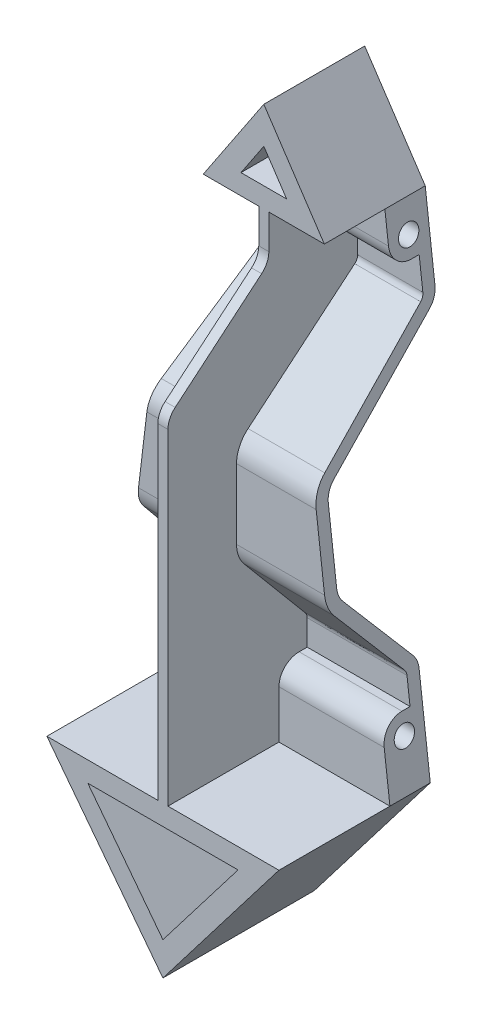
SolidWorks part; units mm, degrees
material "1060 Alloy"
ref_plane "Front Plane" through (0, 0, 0) normal (1, 0, 0) x (0, 1, 0)
ref_plane "Top Plane" through (0, 0, 0) normal (0, 0, 1) x (0, 1, 0)
ref_plane "Right Plane" through (0, 0, 0) normal (0, 1, 0) x (-1, 0, 0)
sketch "Sketch3" plane through (0, 0, 0) normal (1, 0, 0) x (0, 1, 0)
  line L0 (206.8578, 33.9279) -> (242.818, -8.9279)
  line L1 (-37.5, 37.5) -> (37.5, 37.5)
  line L2 (-37.5, 37.5) -> (-37.5, -37.5)
  line L3 (-37.5, -37.5) -> (37.5, -37.5)
  line L4 (37.5, 37.5) -> (37.5, -37.5)
  line L5 (-37.5, 37.5) -> (37.5, -37.5) construction
  line L6 (-37.5, -37.5) -> (37.5, 37.5) construction
  line L7 (37.5, 37.5) -> (199.1973, 37.5)
  line L8 (250.4785, -12.5) -> (267.5, -12.5)
  line L9 (267.5, -20.8097) -> (267.5, -62.5)
  line L10 (267.5, -62.5) -> (227.1631, -62.5)
  line L11 (219.5026, -58.9279) -> (175.1514, -6.0721)
  line L12 (167.4909, -2.5) -> (132.8511, -2.5)
  line L13 (126.4232, -4.8396) -> (90.2882, -35.1604)
  line L14 (83.8603, -37.5) -> (37.5, -37.5)
  line L15 (267.5, -12.5) -> (312.5, -12.5)
  line L16 (267.5, -12.5) -> (267.5, -62.5)
  line L17 (267.5, -62.5) -> (312.5, -62.5)
  line L18 (312.5, -12.5) -> (312.5, -62.5)
  arc A0 (206.8578, 33.9279) -> (199.1973, 37.5) centre (199.1973, 27.5) ccw
  arc A1 (242.818, -8.9279) -> (250.4785, -12.5) centre (250.4785, -2.5) ccw
  arc A2 (227.1631, -62.5) -> (219.5026, -58.9279) centre (227.1631, -52.5) cw
  arc A3 (175.1514, -6.0721) -> (167.4909, -2.5) centre (167.4909, -12.5) ccw
  arc A4 (132.8511, -2.5) -> (126.4232, -4.8396) centre (132.8511, -12.5) ccw
  arc A5 (90.2882, -35.1604) -> (83.8603, -37.5) centre (83.8603, -27.5) cw
  point P0 (0, 0)
  point P22 (222.5, -62.5)
  point P29 (87.5, -37.5)
  dimension "D13" = 10
  dimension "D14" = 10
  dimension "D15" = 10
  dimension "D1" = 75
  dimension "D2" = 75
  dimension "D3" = 50
  dimension "D4" = 45
  dimension "D5" = 60
  dimension "D6" = 35
  dimension "D7" = 130
  dimension "D8" = 230
  dimension "D11" = 50
  dimension "D9" = 50
  dimension "D10" = 50
  dimension "D12" = 45
extrude "Boss-Extrude1" add sketch "Sketch3" along normal mid plane 115 contours L4 L1 L2 L3 | A5 L13 A4 L12 A3 L11 A2 L10 L9 L4 L14 | L18 L15 L16 L9 L17 region at (0, 222.9167, 10.8879) region at (0, 0, 0) region at (0, 290, -37.5)
sketch "Sketch4" plane through (0, 0, 37.5) normal (0, 0, 1) x (1, 0, 0)
  line L0 (0, 390.4065) -> (0, -108.3244) construction
  line L1 (0, -37.5) -> (-57.5, 37.5)
  line L3 (-57.5, 37.5) -> (57.5, 37.5)
  line L5 (57.5, 37.5) -> (0, -37.5)
  line L6 (-57.5, 37.5) -> (-30, 267.5)
  line L7 (0, 294.4722) -> (-11.3148, 277.5)
  line L8 (-30, 267.5) -> (30, 267.5)
  line L10 (57.5, 37.5) -> (30, 267.5)
  line L11 (-30, 267.5) -> (0, 312.5)
  line L12 (57.5, 312.5) -> (-57.5, 312.5) construction
  line L13 (0, 312.5) -> (30, 267.5)
  line L14 (-11.3148, 277.5) -> (11.3148, 277.5)
  line L15 (11.3148, 277.5) -> (0, 294.4722)
  line L16 (-37.2326, 27.5) -> (37.2326, 27.5)
  line L17 (37.2326, 27.5) -> (0, -21.0643)
  line L18 (0, -21.0643) -> (-37.2326, 27.5)
  line L20 (-57.5, 250.4785) -> (-57.5, 312.5) construction
  line L22 (57.5, 250.4785) -> (57.5, 312.5) construction
  line L24 (-57.5, 312.5) -> (57.5, 312.5)
  line L26 (-57.5, 250.4785) -> (-57.5, 312.5)
  line L27 (57.5, 312.5) -> (-57.5, 312.5)
  line L28 (57.5, 250.4785) -> (57.5, 312.5)
  line L38 (-57.5, -37.5) -> (57.5, -37.5)
  line L39 (57.5, 312.5) -> (57.5, -37.5)
  line L40 (-57.5, 312.5) -> (57.5, 312.5)
  line L41 (-57.5, 312.5) -> (-57.5, -37.5)
  line L42 (-57.5, -37.5) -> (57.5, -37.5)
  line L43 (57.5, 312.5) -> (57.5, -37.5)
  dimension "D1" = 75
  dimension "D2" = 230
  dimension "D3" = 30
  dimension "D4" = 10
  dimension "D5" = 10
  dimension "D6" = 10
  dimension "D7" = 10
extrude "Cut-Extrude1" cut sketch "Sketch4" against normal through all contours L5 | L1 | L0 L16 L18 | L16 L0 L17 | L10 | L6 | L28 L27 L13 L10 | L6 L11 L27 L26 | L0 L7 L14 | L15 L0 L14 region at (43.4472, 229.2016, 37.5) region at (-43.4472, 229.2016, 37.5) region at (3.7716, 283.1574, 37.5) region at (-3.7716, 283.1574, 37.5) region at (-38.3333, -12.5, 37.5) region at (38.3333, -12.5, 37.5) region at (-12.4109, 11.3119, 37.5) region at (12.4109, 11.3119, 37.5)
sketch "Sketch6" plane through (61.1101, 7.3066, 0) normal (0.9929, 0.1187, 0) x (-0.1187, 0.9929, 0)
  line L0 (30.4084, -31.5) -> (77.0989, -31.5)
  line L1 (79.7319, -30.5507) -> (116.1243, -0.2298)
  line L2 (126.4386, 3.5) -> (161.3252, 3.5)
  line L3 (173.623, -2.1993) -> (218.2901, -55.0551)
  line L4 (221.4224, -56.5) -> (262.0466, -56.5)
  line L10 (30.4084, 37.5) -> (30.4084, -37.5)
  line L11 (30.4084, -37.5) -> (77.0989, -37.5)
  line L12 (83.5726, -35.1604) -> (119.965, -4.8396)
  line L13 (126.4386, -2.5) -> (161.3252, -2.5)
  line L14 (169.0402, -6.0721) -> (213.7074, -58.9279)
  line L15 (221.4224, -62.5) -> (262.0466, -62.5)
  line L16 (262.0466, -62.5) -> (262.0466, -12.5)
  line L19 (30.4084, 37.5) -> (30.4084, -37.5)
  line L20 (30.4084, -37.5) -> (77.0989, -37.5)
  line L21 (83.5726, -35.1604) -> (119.965, -4.8396)
  line L22 (126.4386, -2.5) -> (161.3252, -2.5)
  line L23 (169.0402, -6.0721) -> (213.7074, -58.9279)
  line L24 (221.4224, -62.5) -> (262.0466, -62.5)
  line L25 (262.0466, -62.5) -> (262.0466, -12.5)
  line L33 (262.0466, -12.5) -> (244.9038, -12.5)
  line L34 (237.1888, -8.9279) -> (200.9724, 33.9279)
  line L35 (237.1888, -8.9279) -> (200.9724, 33.9279)
  line L36 (193.2574, 37.5) -> (30.4084, 37.5)
  line L37 (193.2574, 37.5) -> (30.4084, 37.5)
  line L38 (262.0466, -12.5) -> (244.9038, -12.5)
  ellipse E5 centre (77.0989, -27.5) end of major axis (87.1701, -27.5) minor radius 10 (77.0989, -37.5) -> (83.5726, -35.1604) ccw
  ellipse E6 centre (126.4386, -12.5) end of major axis (136.5099, -12.5) minor radius 10 (126.4386, -2.5) -> (119.965, -4.8396) ccw
  ellipse E7 centre (161.3252, -12.5) end of major axis (171.3965, -12.5) minor radius 10 (169.0402, -6.0721) -> (161.3252, -2.5) ccw
  ellipse E8 centre (221.4224, -52.5) end of major axis (231.4936, -52.5) minor radius 10 (213.7074, -58.9279) -> (221.4224, -62.5) ccw
  ellipse E10 centre (77.0989, -27.5) end of major axis (87.1701, -27.5) minor radius 10 (77.0989, -37.5) -> (83.5726, -35.1604) ccw
  ellipse E11 centre (126.4386, -12.5) end of major axis (136.5099, -12.5) minor radius 10 (126.4386, -2.5) -> (119.965, -4.8396) ccw
  ellipse E12 centre (161.3252, -12.5) end of major axis (171.3965, -12.5) minor radius 10 (169.0402, -6.0721) -> (161.3252, -2.5) ccw
  ellipse E13 centre (221.4224, -52.5) end of major axis (231.4936, -52.5) minor radius 10 (213.7074, -58.9279) -> (221.4224, -62.5) ccw
  ellipse E15 centre (244.9038, -2.5) end of major axis (254.9751, -2.5) minor radius 10 (237.1888, -8.9279) -> (244.9038, -12.5) ccw
  ellipse E16 centre (244.9038, -2.5) end of major axis (254.9751, -2.5) minor radius 10 (237.1888, -8.9279) -> (244.9038, -12.5) ccw
  ellipse E18 centre (193.2574, 27.5) end of major axis (203.3287, 27.5) minor radius 10 (200.9724, 33.9279) -> (193.2574, 37.5) ccw
  ellipse E19 centre (193.2574, 27.5) end of major axis (203.3287, 27.5) minor radius 10 (200.9724, 33.9279) -> (193.2574, 37.5) ccw
  spline S0 degree 1 poles (77.0989, -31.5) (79.7319, -30.5507) knots 0 0 1 1 construction
  spline S1 degree 1 poles (126.4386, 3.5) (116.1243, -0.2298) knots 0 0 1 1 construction
  spline S2 degree 1 poles (173.623, -2.1993) (161.3252, 3.5) knots 0 0 1 1 construction
  spline S3 degree 1 poles (218.2901, -55.0551) (221.4224, -56.5) knots 0 0 1 1 construction
  spline S4 degree 3 poles (77.0989, -31.5) (77.3378, -31.5) (77.8171, -31.4584) (78.5116, -31.2735) (79.1615, -30.9724) (79.5506, -30.7018) (79.7319, -30.5507) knots -1.570796 -1.570796 -1.570796 -1.570796 -1.396263 -1.22173 -1.047198 -0.872665 -0.872665 -0.872665 -0.872665
  spline S5 degree 3 poles (116.1243, -0.2298) (116.8401, 0.3665) (118.379, 1.4365) (120.9273, 2.616) (123.6406, 3.338) (125.5073, 3.5) (126.4386, 3.5) knots 1.570796 1.570796 1.570796 1.570796 1.745329 1.919862 2.094395 2.268928 2.268928 2.268928 2.268928
  spline S6 degree 3 poles (161.3252, 3.5) (162.4886, 3.5) (164.8231, 3.2466) (168.1557, 2.1229) (171.1689, 0.3084) (172.8718, -1.3104) (173.623, -2.1993) knots 0.698132 0.698132 0.698132 0.698132 0.916298 1.134464 1.35263 1.570796 1.570796 1.570796 1.570796
  spline S7 degree 3 poles (218.2901, -55.0551) (218.4793, -55.279) (218.9069, -55.6856) (219.6727, -56.1474) (220.5246, -56.4349) (221.124, -56.5) (221.4224, -56.5) knots -2.443461 -2.443461 -2.443461 -2.443461 -2.225295 -2.007129 -1.788962 -1.570796 -1.570796 -1.570796 -1.570796
  dimension "D1" = 0
  dimension "D2" = 6
sketch "Sketch5" plane through (0, 0, 37.5) normal (0, 0, 1) x (1, 0, 0)
  line L7 (-30, 267.5) -> (30, 267.5) construction
  line L8 (57.5, 37.5) -> (30, 267.5) construction
  line L9 (-30, 267.5) -> (0, 312.5) construction
  line L10 (0, 312.5) -> (30, 267.5) construction
  line L11 (-57.5, 37.5) -> (57.5, 37.5) construction
  line L12 (0, -37.5) -> (-57.5, 37.5) construction
  line L13 (57.5, 37.5) -> (0, -37.5) construction
  line L14 (-57.5, 37.5) -> (-30, 267.5) construction
  line L16 (57.5, 312.5) -> (-57.5, 312.5) construction
  line L18 (37.2326, 27.5) -> (0, -21.0643) construction
  line L19 (0, -21.0643) -> (-37.2326, 27.5) construction
  line L20 (-37.2326, 27.5) -> (37.2326, 27.5) construction
  line L21 (0, 294.4722) -> (-11.3148, 277.5) construction
  line L22 (-11.3148, 277.5) -> (11.3148, 277.5) construction
  line L23 (11.3148, 277.5) -> (0, 294.4722) construction
  line L31 (-30, 267.5) -> (30, 267.5)
  line L32 (57.5, 37.5) -> (30, 267.5)
  line L33 (-30, 267.5) -> (0, 312.5)
  line L34 (0, 312.5) -> (30, 267.5)
  line L35 (-57.5, 37.5) -> (57.5, 37.5)
  line L36 (0, -37.5) -> (-57.5, 37.5)
  line L37 (57.5, 37.5) -> (0, -37.5)
  line L38 (-57.5, 37.5) -> (-30, 267.5)
  line L40 (57.5, 312.5) -> (-57.5, 312.5)
  line L42 (37.2326, 27.5) -> (0, -21.0643)
  line L43 (0, -21.0643) -> (-37.2326, 27.5)
  line L44 (-37.2326, 27.5) -> (37.2326, 27.5)
  line L45 (0, 294.4722) -> (-11.3148, 277.5)
  line L46 (-11.3148, 277.5) -> (11.3148, 277.5)
  line L47 (11.3148, 277.5) -> (0, 294.4722)
  line L55 (-30, 267.5) -> (30, 267.5)
  line L56 (57.5, 37.5) -> (30, 267.5)
  line L57 (-30, 267.5) -> (0, 312.5)
  line L58 (0, 312.5) -> (30, 267.5)
  line L59 (-57.5, 37.5) -> (57.5, 37.5)
  line L60 (0, -37.5) -> (-57.5, 37.5)
  line L61 (57.5, 37.5) -> (0, -37.5)
  line L62 (-57.5, 37.5) -> (-30, 267.5)
  line L64 (57.5, 312.5) -> (-57.5, 312.5)
  line L66 (37.2326, 27.5) -> (0, -21.0643)
  line L67 (0, -21.0643) -> (-37.2326, 27.5)
  line L68 (-37.2326, 27.5) -> (37.2326, 27.5)
  line L69 (0, 294.4722) -> (-11.3148, 277.5)
  line L70 (-11.3148, 277.5) -> (11.3148, 277.5)
  line L71 (11.3148, 277.5) -> (0, 294.4722)
  line L72 (0, -37.5) -> (0, 312.5) construction
  line L73 (2.5, -37.5) -> (2.5, 312.5)
  line L74 (-2.5, -37.5) -> (-2.5, 312.5)
  line L75 (-57.5, 312.5) -> (57.5, 312.5)
  line L76 (-57.5, 312.5) -> (-57.5, -37.5)
  line L77 (-57.5, -37.5) -> (57.5, -37.5)
  line L78 (57.5, 312.5) -> (57.5, -37.5)
  dimension "D1" = 2.5
  dimension "D2" = 2.5
ref_plane "Plane1" through (0, 0, 0) normal (1, 0, 0) x (0, 1, 0)
sketch "Sketch7" plane through (0, 0, 0) normal (1, 0, 0) x (0, 1, 0)
  line L0 (37.5, -31.5) -> (83.8603, -31.5) construction
  line L1 (86.4747, -30.5507) -> (122.6097, -0.2298) construction
  line L2 (132.8511, 3.5) -> (167.4909, 3.5) construction
  line L3 (179.7017, -2.1993) -> (224.053, -55.0551) construction
  line L4 (227.1631, -56.5) -> (267.5, -56.5) construction
  line L5 (37.5, -31.5) -> (83.8603, -31.5)
  line L6 (86.4747, -30.5507) -> (122.6097, -0.2298)
  line L7 (132.8511, 3.5) -> (167.4909, 3.5)
  line L8 (179.7017, -2.1993) -> (224.053, -55.0551)
  line L10 (37.5, 37.5) -> (37.5, -37.5)
  line L11 (37.5, -37.5) -> (83.8603, -37.5)
  line L12 (90.2882, -35.1604) -> (126.4232, -4.8396)
  line L13 (132.8511, -2.5) -> (167.4909, -2.5)
  line L14 (175.1514, -6.0721) -> (219.5026, -58.9279)
  line L15 (227.1631, -62.5) -> (267.5, -62.5)
  line L16 (267.5, -62.5) -> (267.5, -12.5)
  line L19 (37.5, 37.5) -> (37.5, -37.5)
  line L20 (37.5, -37.5) -> (83.8603, -37.5)
  line L21 (90.2882, -35.1604) -> (126.4232, -4.8396)
  line L22 (132.8511, -2.5) -> (167.4909, -2.5)
  line L23 (175.1514, -6.0721) -> (219.5026, -58.9279)
  line L24 (227.1631, -62.5) -> (267.5, -62.5)
  line L25 (267.5, -62.5) -> (267.5, -12.5)
  line L27 (227.1631, -56.5) -> (267.5, -56.5)
  line L37 (267.5, -12.5) -> (250.4785, -12.5)
  line L38 (242.818, -8.9279) -> (206.8578, 33.9279)
  line L39 (242.818, -8.9279) -> (206.8578, 33.9279)
  line L40 (199.1973, 37.5) -> (37.5, 37.5)
  line L41 (199.1973, 37.5) -> (37.5, 37.5)
  line L42 (267.5, -12.5) -> (250.4785, -12.5)
  arc A6 (83.8603, -37.5) -> (90.2882, -35.1604) centre (83.8603, -27.5) ccw
  arc A7 (132.8511, -2.5) -> (126.4232, -4.8396) centre (132.8511, -12.5) ccw
  arc A8 (175.1514, -6.0721) -> (167.4909, -2.5) centre (167.4909, -12.5) ccw
  arc A9 (219.5026, -58.9279) -> (227.1631, -62.5) centre (227.1631, -52.5) ccw
  arc A10 (242.818, -8.9279) -> (250.4785, -12.5) centre (250.4785, -2.5) ccw
  arc A12 (83.8603, -37.5) -> (90.2882, -35.1604) centre (83.8603, -27.5) ccw
  arc A13 (132.8511, -2.5) -> (126.4232, -4.8396) centre (132.8511, -12.5) ccw
  arc A14 (175.1514, -6.0721) -> (167.4909, -2.5) centre (167.4909, -12.5) ccw
  arc A15 (219.5026, -58.9279) -> (227.1631, -62.5) centre (227.1631, -52.5) ccw
  arc A18 (206.8578, 33.9279) -> (199.1973, 37.5) centre (199.1973, 27.5) ccw
  arc A19 (206.8578, 33.9279) -> (199.1973, 37.5) centre (199.1973, 27.5) ccw
  arc A20 (242.818, -8.9279) -> (250.4785, -12.5) centre (250.4785, -2.5) ccw
  spline S0 degree 3 poles (1036.847, 271.5103) (41.5641, 38.2935) (70.896, -35.1255) (85.263, -31.2735) (101.385, -23.7509) (57.2342, 79.1045) (-857.6254, -360.1774) knots -11.955085 -11.955085 -11.955085 -11.955085 -1.396263 -1.22173 -1.047198 11.684815 11.684815 11.684815 11.684815 only from (83.8603, -31.5) to (86.4747, -30.5507) construction
  spline S1 degree 3 poles (1097.2215, 223.6638) (124.1784, -149.5889) (91.9137, -13.9155) (127.3787, 2.616) (165.4231, 12.8125) (227.1208, -113.8572) (-762.4737, -441.8839) knots -5.244568 -5.244568 -5.244568 -5.244568 1.745329 1.919862 2.094395 9.139196 9.139196 9.139196 9.139196 only from (122.6097, -0.2298) to (132.8511, 3.5) construction
  spline S2 degree 3 poles (1055.3487, -456.618) (68.2809, -110.6838) (136.3378, 15.0053) (174.2731, 2.1229) (208.2767, -18.4985) (158.087, -150.5745) (-747.8475, 371.4445) knots -6.150752 -6.150752 -6.150752 -6.150752 0.916298 1.134464 1.35263 8.354662 8.354662 8.354662 8.354662 only from (167.4909, 3.5) to (179.7017, -2.1993) construction
  spline S3 degree 3 poles (1096.5444, -543.6842) (265.4259, 45.5151) (210.4211, -47.0341) (225.4258, -56.1474) (239.6739, -60.9892) (272.8276, 11.8595) (-719.6849, 265.1571) knots -14.70434 -14.70434 -14.70434 -14.70434 -2.225295 -2.007129 -1.788962 8.799645 8.799645 8.799645 8.799645 only from (224.053, -55.0551) to (227.1631, -56.5) construction
  spline S4 degree 3 poles (83.8603, -31.5) (84.0975, -31.5) (84.5734, -31.4584) (85.263, -31.2735) (85.9083, -30.9724) (86.2946, -30.7018) (86.4747, -30.5507) knots -1.570796 -1.570796 -1.570796 -1.570796 -1.396263 -1.22173 -1.047198 -0.872665 -0.872665 -0.872665 -0.872665
  spline S5 degree 3 poles (122.6097, -0.2298) (123.3204, 0.3665) (124.8484, 1.4365) (127.3787, 2.616) (130.0728, 3.338) (131.9263, 3.5) (132.8511, 3.5) knots 1.570796 1.570796 1.570796 1.570796 1.745329 1.919862 2.094395 2.268928 2.268928 2.268928 2.268928
  spline S6 degree 3 poles (167.4909, 3.5) (168.6461, 3.5) (170.9641, 3.2466) (174.2731, 2.1229) (177.265, 0.3084) (178.9559, -1.3104) (179.7017, -2.1993) knots 0.698132 0.698132 0.698132 0.698132 0.916298 1.134464 1.35263 1.570796 1.570796 1.570796 1.570796
  spline S7 degree 3 poles (224.053, -55.0551) (224.2409, -55.279) (224.6654, -55.6856) (225.4258, -56.1474) (226.2716, -56.4349) (226.8668, -56.5) (227.1631, -56.5) knots -2.443461 -2.443461 -2.443461 -2.443461 -2.225295 -2.007129 -1.788962 -1.570796 -1.570796 -1.570796 -1.570796
  dimension "D1" = 0
extrude "Cut-Extrude4" cut sketch "Sketch7" along normal through all from offset 2.5 contours L8 S7 L27 L25 L19 L5 S4 L6 S5 L7 S6 region at (0, 39.9847, 3)
mirror "Mirror1" about plane through (0, 0, 0) normal (1, 0, 0) of "Cut-Extrude4"
sketch "Sketch9" plane through (0, 0, 0) normal (1, 0, 0) x (0, 1, 0)
  line L0 (37.5, -17.5) -> (61.25, -17.5)
  line L1 (37.5, 37.5) -> (37.5, -37.5) construction
  line L2 (71.25, -27.5) -> (71.25, -37.5)
  line L3 (37.5, -37.5) -> (83.8603, -37.5) construction
  line L4 (267.5, -42.5) -> (252.5, -42.5)
  line L5 (267.5, -62.5) -> (267.5, -12.5) construction
  line L6 (242.5, -52.5) -> (242.5, -62.5)
  line L7 (227.1631, -62.5) -> (267.5, -62.5) construction
  line L8 (267.5, -62.5) -> (267.5, -12.5)
  line L9 (227.1631, -62.5) -> (267.5, -62.5)
  line L10 (37.5, -37.5) -> (83.8603, -37.5)
  line L11 (37.5, 37.5) -> (37.5, -37.5)
  arc A0 (61.25, -17.5) -> (71.25, -27.5) centre (61.25, -27.5) cw
  circle A1 centre (61.25, -27.5) radius 5
  arc A2 (252.5, -42.5) -> (242.5, -52.5) centre (252.5, -52.5) ccw
  circle A3 centre (252.5, -52.5) radius 5
  point P10 (49.375, -17.5)
  dimension "D4" = 10
  dimension "D6" = 10
  dimension "D7" = 10
  dimension "D1" = 10
  dimension "D2" = 10
  dimension "D3" = 20
  dimension "D5" = 23.75
  dimension "D8" = 15
  dimension "D9" = 10
  dimension "D10" = 10
  dimension "D11" = 20
extrude "Boss-Extrude2" add sketch "Sketch9" along normal up to surface and the other way up to surface contours A0 L0 L11 L10 L2 A1 | L4 A2 L6 L9 L8 A3 region at (0, 52.8895, -27.7899) region at (0, 267.1798, -52.5) up to face at (43.665, 153.211, -28.3196) other way up to face at (-43.7501, 152.4994, -28.2572)
extrude "Cut-Extrude5" cut sketch "Sketch9<3>" against normal through all both and the other way through all contours A1 | A3
sketch "Sketch9<3>" plane through (0, 0, 0) normal (1, 0, 0) x (0, 1, 0) same geometry as "Sketch9"
equation "\"B\"= 75"
equation "\"A\"= 230"
equation "\"Y\"= ( 2 * \"B\" ) / 3"
equation "\"x\"= \"A\" / 4"
equation "\"D1@Sketch3\"=\"B\""
equation "\"D2@Sketch3\"=\"B\""
equation "\"D8@Sketch3\"=\"A\""
equation "\"D9@Sketch3\"=\"Y\""
equation "\"D10@Sketch3\"=\"Y\""
equation "\"D1@Boss-Extrude1\"=2 * \"x\""
equation "\"D1@Sketch4\"=\"B\""
equation "\"D2@Sketch4\"= \"A\""
equation "\"z\"= ( \"A\" / 8 ) - 5"
equation "\"D5@Sketch9\"=\"z\""
